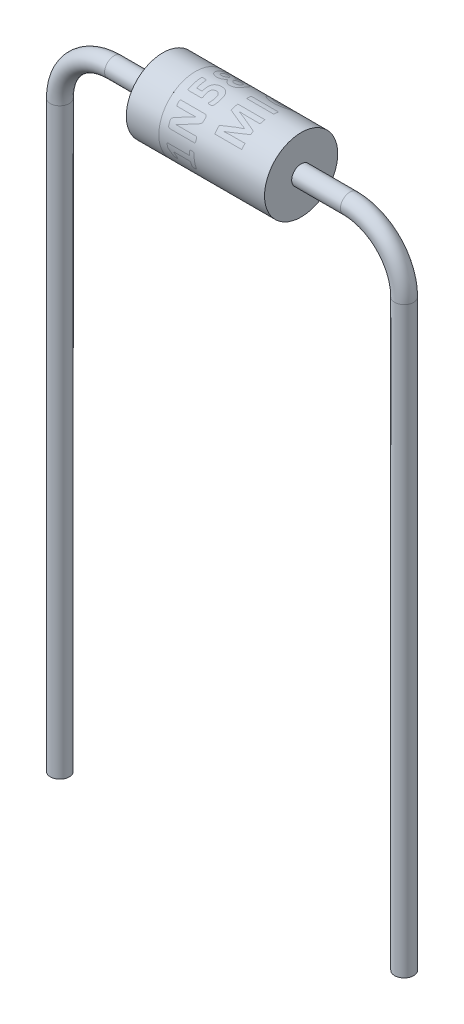
SolidWorks part; units mm, degrees
other "Wire"
other "Cathode Silver Band"
other "Diode"
ref_plane "Front Plane" through (0, 0, 0) normal (0, 0, 1) x (1, 0, 0)
ref_plane "Top Plane" through (0, 0, 0) normal (0, 1, 0) x (1, 0, 0)
ref_plane "Right Plane" through (0, 0, 0) normal (1, 0, 0) x (0, 0, -1)
sketch "Sketch1" plane through (0, 0, 0) normal (1, 0, 0) x (0, 0, -1)
  circle A0 centre (0, 0) radius 1.35
  circle A1 centre (0, 0) radius 0.35
  dimension "D1" = 2.7
  dimension "D2" = 0.7
extrude "Boss-Extrude1" add sketch "Sketch1" along normal mid plane 5.1
sketch "Sketch2" plane through (-2.55, 0, 0) normal (-1, 0, 0) x (0, 0, 1)
  circle A1 centre (0, 0) radius 1.35 construction
  circle A2 centre (0, 0) radius 1.34
  circle A3 centre (0, 0) radius 1.34
  circle A4 centre (0, 0) radius 1.35
  dimension "D1" = 0.01
extrude "Cut-Extrude1" cut sketch "Sketch2" against normal blind 1.2
sketch "Sketch3" plane through (-1.35, 0, 0) normal (-1, 0, 0) x (0, 0, 1)
  circle A0 centre (0, 0) radius 1.34 construction
  circle A1 centre (0, 0) radius 1.34
  circle A2 centre (0, 0) radius 1.35 construction
  circle A3 centre (0, 0) radius 1.35
extrude "Boss-Extrude2" add sketch "Sketch3" along normal up to surface (1.2 mm away) separate body up to face at (-2.55, 0, -0.35)
ref_plane "Plane1" through (0, 5, 0) normal (0, 1, 0) x (1, 0, 0)
sketch "Sketch4" plane through (0, 5, 0) normal (0, 1, 0) x (1, 0, 0)
  line L0 (-0.05, 7.5) -> (-0.05, -7.5) construction
  line L1 (-0.05, 0) -> (-2.55, 0) construction
  line L2 (-2.55, 1.35) -> (-2.55, -1.35) construction
  line L4 (-0.05, 0) -> (1.45, 0) construction
  line L5 (1.45, 7.5) -> (1.45, -7.5) construction
  text T0 "1N5817" font "Calibri" height 1
  text T1 "MIC" font "Corbel" height 1
  dimension "D1" = 2.5
  dimension "D2" = 15
  dimension "D3" = 1.5
wrap "Wrap1" sketch "Sketch4" wrap type scribe source sketch "Sketch4" face at (2.55, 0, -1.35)
sketch "Sketch5" plane through (0, 0, 0) normal (0, 0, 1) x (1, 0, 0)
  line L0 (0, 0) -> (-4.35, 0)
  line L1 (-6.35, -2) -> (-6.35, -23.5084)
  line L2 (0, 0) -> (4.35, 0)
  line L3 (6.35, -2) -> (6.35, -23.5084)
  arc A0 (-4.35, 0) -> (-6.35, -2) centre (-4.35, -2) ccw
  arc A1 (4.35, 0) -> (6.35, -2) centre (4.35, -2) cw
  dimension "D2" = 2
  dimension "D3" = 58
  dimension "D1" = 12.7
sketch "Sketch6" plane through (0, 0, 0) normal (1, 0, 0) x (0, 0, -1)
  circle A0 centre (0, 0) radius 0.35
  dimension "D1" = 0.7
sweep "Sweep1" add profiles "Sketch6" path "Sketch5"
